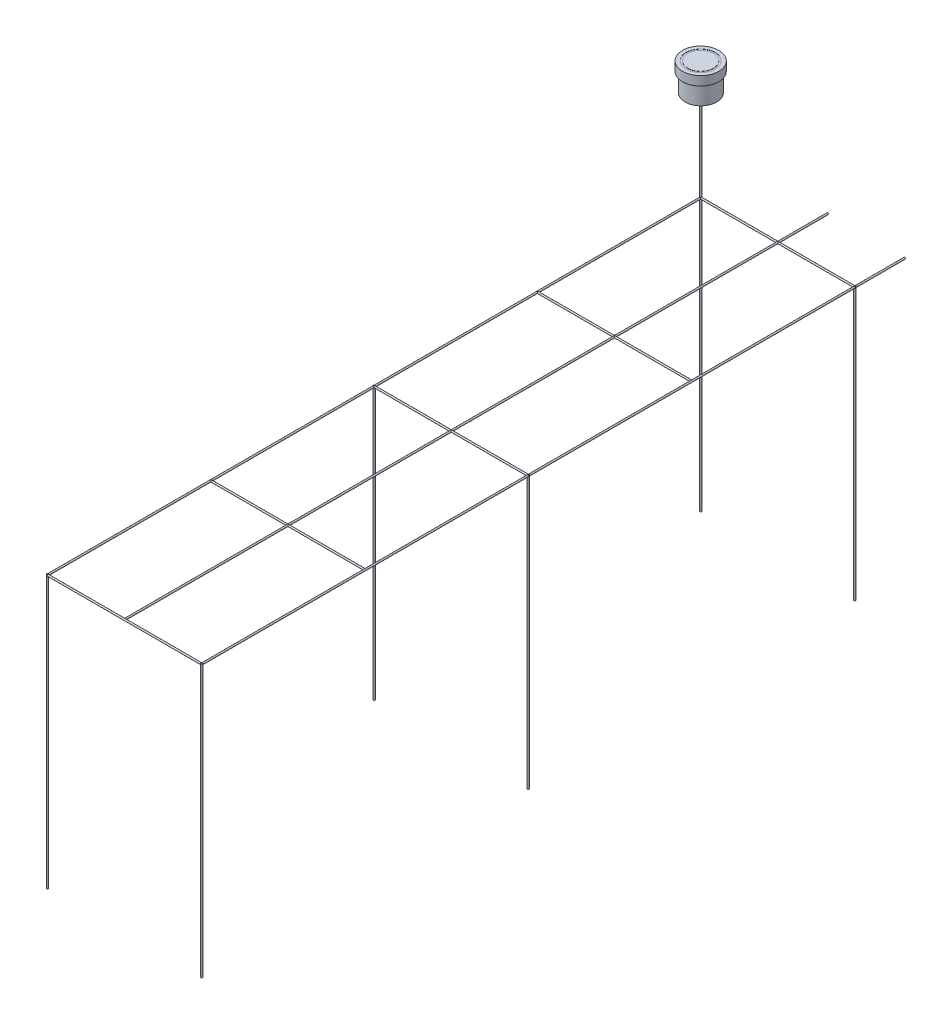
SolidWorks part; units mm, degrees
ref_plane "Alzado" through (0, 0, 0) normal (0, 0, 1) x (1, 0, 0)
ref_plane "Planta" through (0, 0, 0) normal (0, 1, 0) x (1, 0, 0)
ref_plane "Vista lateral" through (0, 0, 0) normal (1, 0, 0) x (0, 0, -1)
sketch "Croquis1" plane through (0, 0, 0) normal (0, 1, 0) x (1, 0, 0)
  circle A0 centre (0, 0) radius 9
  dimension "D1" = 18
extrude "Saliente-Extruir1" add sketch "Croquis1" against normal blind 3000
sketch "Croquis2" plane through (0, 0, 0) normal (0, 0, 1) x (1, 0, 0)
  line L0 (0, 0) -> (0, -9) construction
  circle A0 centre (0, -9) radius 9
  dimension "D1" = 9
extrude "Saliente-Extruir2" add sketch "Croquis2" against normal blind 7200
pattern_linear "MatrizL2" count 3 spacing 3600 along (0, 0, -1) of "Saliente-Extruir1"
sketch "Croquis3" plane through (0, 0, 0) normal (1, 0, 0) x (0, 0, -1)
  line L0 (0, 0) -> (0, -9) construction
  line L1 (0, -9) -> (9, -18) construction
  line L2 (0, -9) -> (9, 0) construction
  circle A0 centre (0, -9) radius 9
extrude "Saliente-Extruir3" add sketch "Croquis3" along normal blind 1700
sketch "Croquis5" plane through (0, 0, 0) normal (0, 0, 1) x (1, 0, 0)
  line L0 (1700, -9) -> (1704.5, -9) construction
  line L1 (1700, -18) -> (1700, 0) construction
  circle A0 centre (1704.5, -9) radius 4.5
  dimension "D1" = 4.5
pattern_linear "MatrizL3" count 2 spacing 1700 along (1, 0, 0) of "Saliente-Extruir1"
sketch "Croquis6" plane through (0, 0, 0) normal (0, 1, 0) x (1, 0, 0)
  circle A0 centre (0, 7200) radius 9
extrude "Saliente-Extruir5" add sketch "Croquis6" along normal blind 1300
sketch "Croquis7" plane through (0, 1300, 0) normal (0, 1, 0) x (1, 0, 0)
  circle A0 centre (0, 7200) radius 200
  dimension "D1" = 400
extrude "Saliente-Extruir6" add sketch "Croquis7" against normal blind 100
sketch "Croquis8" plane through (0, 1200, 0) normal (0, -1, 0) x (1, 0, 0)
  circle A0 centre (7.482, -7194.998) radius 175
  circle A1 centre (0, -7200) radius 9 construction
  dimension "D1" = 350
extrude "Saliente-Extruir7" add sketch "Croquis8" along normal blind 200
sketch "Croquis9" plane through (0, 0, 0) normal (0, 1, 0) x (1, 0, 0)
  line L0 (0, -9) -> (0, 9) construction
ref_plane "Plano1" through (0, 0, 0) normal (1, 0, 0) x (0, 0, -1)
sketch "Croquis11" plane through (0, 0, 0) normal (0, 1, 0) x (1, 0, 0)
  line L0 (1709, 0) -> (1691, 0) construction
  circle A0 centre (1700, 0) radius 9 construction
ref_plane "Plano2" through (0, 0, 0) normal (0, 0, -1) x (-1, 0, 0)
sketch "Croquis12" plane through (0, 0, 0) normal (0, 0, -1) x (-1, 0, 0)
  circle A0 centre (-1700, -9) radius 9
extrude "Saliente-Extruir8" add sketch "Croquis12" along normal blind 7200
pattern_linear "MatrizL4" count 3 spacing 3600 along (0, 0, -1) of "Saliente-Extruir3"
sketch "Croquis13" plane through (0, 0, 0) normal (0, 1, 0) x (1, 0, 0)
  line L0 (0, 3600) -> (1700, 3600) construction
  line L1 (1700, 3600) -> (1691, 3609) construction
  line L2 (1691, 3591) -> (1700, 3600) construction
  line L3 (1700, 3600) -> (1700, 7200) construction
  line L4 (1700, 7200) -> (1686.2491, 7200) construction
  circle A0 centre (0, 3600) radius 9
  circle A1 centre (1700, 3600) radius 9
  circle A2 centre (1700, 7200) radius 9
  dimension "D1" = 18
  dimension "D2" = 18
extrude "Saliente-Extruir10" add sketch "Croquis13" against normal blind 3000
sketch "Croquis14" plane through (0, 0, 0) normal (0, 1, 0) x (1, 0, 0)
  line L0 (1709, 7200) -> (1691, 7200) construction
  line L1 (1709, 3600) -> (1709, 7200) construction
  arc A0 (1700, 7191) -> (1691, 7200) centre (1700, 7200) ccw construction
ref_plane "Plano3" through (0, 0, -7200) normal (0, 0, -1) x (-1, 0, 0)
sketch "Croquis15" plane through (0, 0, -7200) normal (0, 0, -1) x (-1, 0, 0)
  circle A0 centre (-1700, -9) radius 9
  dimension "D1" = 18
extrude "Saliente-Extruir11" add sketch "Croquis15" along normal blind 550
sketch "Croquis17" plane through (0, 0, 0) normal (0, 0, -1) x (-1, 0, 0)
  line L0 (-1700, -9) -> (0, -9) construction
  line L1 (0, -9) -> (-850, -9) construction
  line L2 (-850, -9) -> (-850, 37.8658) construction
  circle A0 centre (-850, -9) radius 9
extrude "Saliente-Extruir12" add sketch "Croquis17" along normal blind 7201
sketch "Croquis18" plane through (0, 0, 0) normal (1, 0, 0) x (0, 0, -1)
  line L0 (0, -9) -> (3600, -9) construction
  line L1 (3600, -9) -> (1800, -9) construction
  line L2 (1800, -9) -> (1800, 87.9518) construction
  line L3 (3600, -9) -> (7200, -9) construction
  line L4 (7200, -9) -> (5400, -9) construction
  line L5 (5400, -9) -> (5400, 222.5881) construction
  circle A0 centre (1800, -9) radius 9
  circle A1 centre (5400, -9) radius 9
extrude "Saliente-Extruir14" add sketch "Croquis18" along normal blind 1700
sketch "Croquis19" plane through (0, 1300, 0) normal (0, 1, 0) x (1, 0, 0)
  circle A0 centre (0, 7200) radius 160
  circle A1 centre (0, 7200) radius 141.6194
  dimension "D1" = 320
extrude "Cortar-Extruir1" cut sketch "Croquis19" against normal blind 2
sketch "Croquis20" plane through (0, 0, -7200) normal (0, 0, -1) x (-1, 0, 0)
  circle A0 centre (-850, -9) radius 9
extrude "Saliente-Extruir15" add sketch "Croquis20" along normal blind 550
sketch "Croquis21" plane through (0, 1300, 0) normal (0, 1, 0) x (1, 0, 0)
  line L0 (850, -9) -> (850, 7209) construction
  line L1 (0, -9) -> (1700, -9) construction
  line L2 (850, 7209) -> (850, 3600) construction
  line L3 (850, 3600) -> (967.8023, 3600) construction
ref_plane "Plano4" through (850, 0, 0) normal (1, 0, 0) x (0, 0, -1)
ref_plane "Plano5" through (0, 0, -3600) normal (0, 0, 1) x (1, 0, 0)
